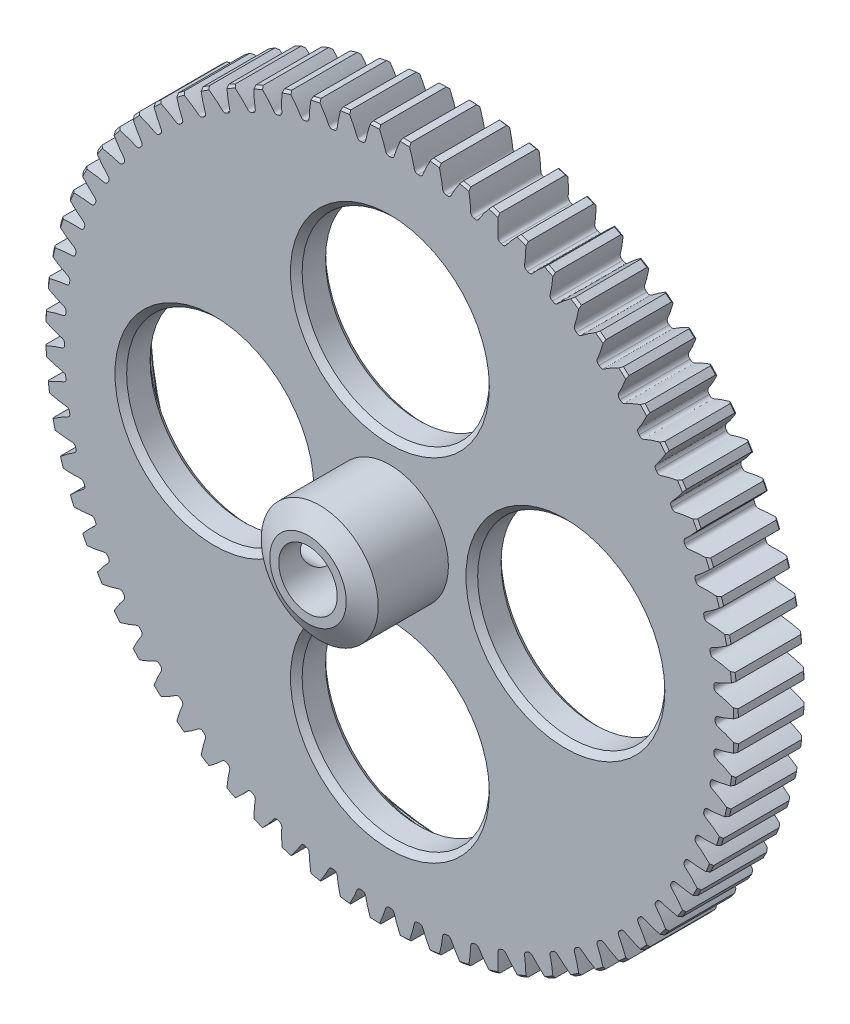
SolidWorks part; units mm, degrees
note: '?' marks a value the reader was unsure of.
ref_plane "Front Plane" through (0, 0, 0) normal (0, 0, 1) x (1, 0, 0)
ref_plane "Top Plane" through (0, 0, 0) normal (0, 1, 0) x (1, 0, 0)
ref_plane "Right Plane" through (0, 0, 0) normal (1, 0, 0) x (0, 0, -1)
ref_axis "Ось вращения" through (0, 0, -7.134) along (0, 0, 1)?
sketch "Gear-BaseSketch" plane through (0, 0, 0) normal (0, 0, 1) x (1, 0, 0)
  circle A0 centre (0, 0) radius 29.6
  dimension "D1" = 59.2
extrude "0.8 Module, 57,6000mm P.D." add sketch "Gear-BaseSketch" along normal mid plane 6
chamfer "Фаска шестерни" distance 0.2 angle 45 2 edges at (29.6, 0, -3) (29.6, 0, 3)
sketch "Tooth-Sketch; Backlash: 0,0000mm" plane through (0, 0, 0) normal (0, 0, 1) x (1, 0, 0)
  line L0 (0, 0) -> (0, 40.5947) construction
  arc A0 (-1.0243, 29.6876) -> (1.0243, 29.6876) centre (0, 0) cw
  spline S0 degree 3 poles (-1.0243, 29.6876) (-0.9796, 29.5974) (-0.9152, 29.4632) (-0.8341, 29.2852) (-0.7776, 29.157) (-0.7244, 29.0321) (-0.6745, 28.9105) (-0.6277, 28.7924) (-0.5839, 28.6777) (-0.5432, 28.5666) (-0.5053, 28.4591) (-0.4701, 28.3552) (-0.4376, 28.2551) (-0.4077, 28.1587) (-0.3868, 28.0883) (-0.3742, 28.0443) (-0.3683, 28.0257) (-0.3623, 28.0088) (-0.3532, 27.9858) (-0.339, 27.9556) (-0.3156, 27.9169) (-0.2796, 27.8739) (-0.185, 27.7997) (-0.0747, 27.7908) (0, 27.7998) knots 0 0 0 0 0.133477 0.197329 0.259255 0.319256 0.377332 0.433483 0.487709 0.54001 0.590386 0.638837 0.685363 0.729963 0.772639 0.782749 0.79059 0.798481 0.806506 0.823418 0.842635 0.866291 0.897399 1 1 1 1
  spline S1 degree 3 poles (1.0243, 29.6876) (0.9796, 29.5974) (0.9152, 29.4632) (0.8341, 29.2852) (0.7776, 29.157) (0.7244, 29.0321) (0.6745, 28.9105) (0.6277, 28.7924) (0.5839, 28.6777) (0.5432, 28.5666) (0.5053, 28.4591) (0.4701, 28.3552) (0.4376, 28.2551) (0.4077, 28.1587) (0.3868, 28.0883) (0.3742, 28.0443) (0.3683, 28.0257) (0.3623, 28.0088) (0.3532, 27.9858) (0.339, 27.9556) (0.3156, 27.9169) (0.2796, 27.8739) (0.185, 27.7997) (0.0747, 27.7908) (0, 27.7998) knots 0 0 0 0 0.133477 0.197329 0.259255 0.319256 0.377332 0.433483 0.487709 0.54001 0.590386 0.638837 0.685363 0.729963 0.772639 0.782749 0.79059 0.798481 0.806506 0.823418 0.842635 0.866291 0.897399 1 1 1 1
extrude "Tooth-Cut, Coarse Pitch Involute 20 deg" cut sketch "Tooth-Sketch; Backlash: 0,0000mm" against normal through all and the other way through all
pattern_circular "Tooth Pattern, 72 / 72" count 72 every 5 about axis through (0, 0, -7.134) along (0, 0, 1) of "Tooth-Cut, Coarse Pitch Involute 20 deg"
sketch "Sketch3" plane through (0, 0, 3) normal (0, 0, 1) x (1, 0, 0)
  circle A0 centre (0, 0) radius 5
extrude "Хвостовик" add sketch "Sketch3" along normal blind 7
sketch "Sketch4" plane through (0, 0, 10) normal (0, 0, 1) x (1, 0, 0)
  circle A0 centre (0, 0) radius 2.5
extrude "Сквозное" cut sketch "Sketch4" against normal blind 13
ref_plane "Plane1" through (0, 0, 0) normal (-1, 0, 0) x (0, 0, 1)
ref_plane "Plane2" through (-5, 0, 0) normal (-1, 0, 0) x (0, 0, 1)
sketch "Sketch5" plane through (0, 0, -3) normal (0, 0, -1) x (-1, 0, 0)
  circle A0 centre (0, 0) radius 26
extrude "Вырез" cut sketch "Sketch5" against normal blind 3
sketch "Sketch6" plane through (0, 0, 0) normal (0, 0, -1) x (-1, 0, 0)
  line L1 (0, -8.8687) -> (0, 8.8687) construction
  circle A2 centre (0, 15) radius 8
  dimension "D1" = 15
extrude "Облегчение" cut sketch "Sketch6" against normal blind 3
pattern_circular "CirPattern2" count 4 over 360 about axis through (0, 0, 0) along (0, 0, 1) of "Облегчение"
chamfer "Общие фаски" distance 0.5 angle 45 10 edges at (8, -15, 3) (8, -15, 0) (-15, -8, 3) (-15, -8, 0) (15, 8, 3) (15, 8, 0) (-8, 15, 3) (-8, 15, 0) (-26, 0, -3) (-2.5, 0, 0)
sketch "Sketch7" plane through (-5, 0, 0) normal (-1, 0, 0) x (0, 0, 1)
  line L2 (10, -2.5) -> (10, 2.5) construction
  circle A0 centre (6.5, 0) radius 1.65
  point P6 (10.9364, 5.4421)
  dimension "D1" = 3.5
extrude "Крепеж" cut sketch "Sketch7" against normal blind 5
cosmetic thread "Cosmetic Thread1" parameters "D2"=4
ref_axis "Ось крепления" through (-1.7546, 0, 6.5) along (-1, 0, 0)?
chamfer "Фаска под подшипник" distance 1 angle 60 1 edges at (5, 0, 10)
equation "\"1ю5\"=1"
